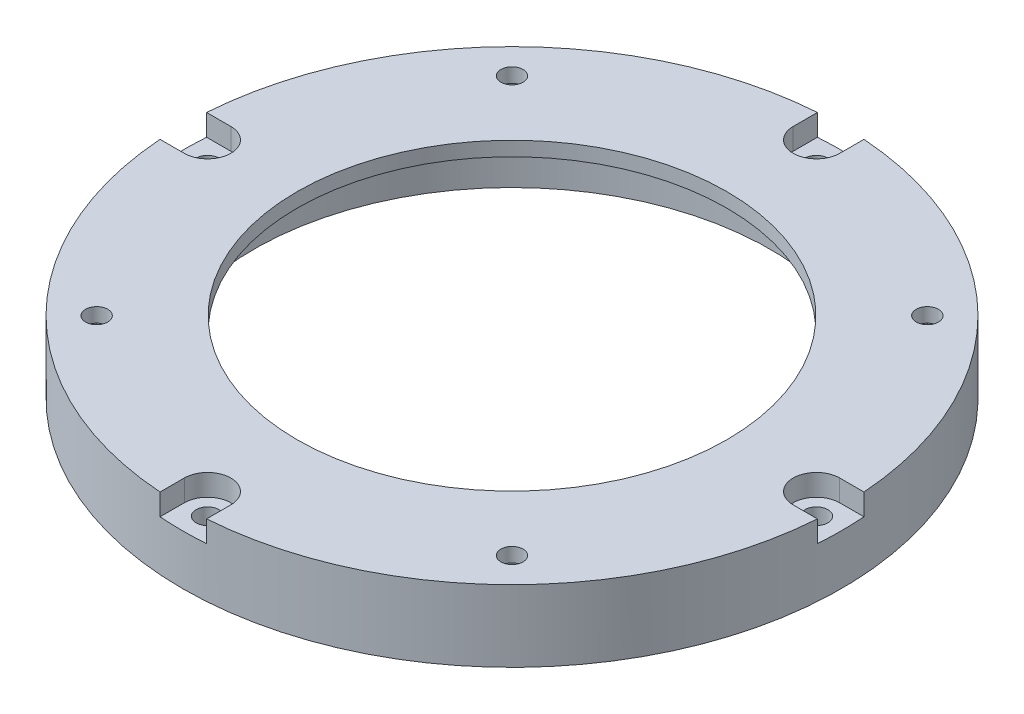
SolidWorks part; units mm, degrees
note: The reader was unsure of these and kept them because the rebuilt part matched: shared geometry of "Sketch1<3>", "Sketch9<3>".
ref_plane "Front Plane" through (0, 0, 0) normal (0, 0, 1) x (1, 0, 0)
ref_plane "Top Plane" through (0, 0, 0) normal (0, 1, 0) x (1, 0, 0)
ref_plane "Right Plane" through (0, 0, 0) normal (1, 0, 0) x (0, 0, -1)
sketch "Sketch1" plane through (0, 0, 0) normal (0, 1, 0) x (1, 0, 0)
  circle A0 centre (0, 0) radius 46
  circle A1 centre (0, 0) radius 36.05
  circle A2 centre (0, 0) radius 30
  dimension "D1" = 60
  dimension "D2" = 72.1
  dimension "D3" = 92
extrude "Boss-Extrude1" add sketch "Sketch1" against normal blind 2 contours A1 A2 | A0 A1
extrude "Boss-Extrude2" add sketch "Sketch1<3>" against normal blind 8 from surface at -2 contours A0 A1 starting at face at (0, -2, 30)
sketch "Sketch1<3>" plane through (0, 0, 0) normal (0, 1, 0) x (1, 0, 0) same geometry as "Sketch1"
hole_wizard "CBORE for M3 SHCS2" positions "Sketch6" profile "Sketch7" counterbore size "M3" standard "ANSI Metric" end condition through all
sketch "Sketch6" plane through (0, 0, 0) normal (0, 1, 0) x (1, 0, 0)
  line L0 (0, 0) -> (-42.5, 0) construction
  point P2 (-42.5, 0)
  dimension "D1" = 42.5
sketch "Sketch7" plane through (-42.5, 0, 0) normal (1, 0, 0) x (0, 0, 1)
  line L0 (0, 0) -> (0, 10)
  line L1 (0, 10) -> (1.6, 10)
  line L3 (1.6, 10) -> (1.6, 3)
  line L4 (1.6, 3) -> (3.25, 3)
  line L5 (3.25, 3) -> (3.25, 0)
  line L7 (3.25, 0) -> (0, 0)
  line L11 (0, -6.35) -> (0, 107.95) construction
  dimension "Thru Hole Dia." = 3.2
  dimension "Thru Hole Depth" = 10
  dimension "C'Bore Dia." = 6.5
  dimension "C'Bore Depth" = 3
sketch "Sketch8" plane through (0, -3, 0) normal (0, 1, 0) x (1, 0, 0)
  line L1 (-42.5, 3.25) -> (-52.5, 3.25)
  line L2 (-42.5, 3.25) -> (-42.5, -3.25)
  line L3 (-42.5, -3.25) -> (-52.5, -3.25)
  line L4 (-52.5, 3.25) -> (-52.5, -3.25)
  circle A3 centre (-42.5, 0) radius 3.25
  circle A5 centre (-42.5, 0) radius 3.25
  dimension "D2" = 10
  dimension "D1" = 0
extrude "Cut-Extrude1" cut sketch "Sketch8" along normal through all
pattern_circular "CirPattern1" count 4 over 360 about axis through (0, 0, 0) along (0, 1, 0) of "Cut-Extrude1", "CBORE for M3 SHCS2"
sketch "Sketch9" plane through (0, 0, 0) normal (0, 1, 0) x (1, 0, 0)
  line L0 (0, 0) -> (28.9914, 28.9914) construction
  line L1 (0, 0) -> (46, 0) construction
  line L2 (26.746, 31.2367) -> (25.9242, 28.1695)
  line L3 (25.9242, 28.1695) -> (28.1695, 25.9242)
  line L4 (28.1695, 25.9242) -> (31.2367, 26.746)
  line L5 (31.2367, 26.746) -> (32.0586, 29.8132)
  line L6 (32.0586, 29.8132) -> (29.8132, 32.0586)
  line L7 (29.8132, 32.0586) -> (26.746, 31.2367)
  circle A0 centre (28.9914, 28.9914) radius 1.55
  circle A1 centre (28.9914, 28.9914) radius 2.75 construction
  arc A2 (45.885, -3.25) -> (45.885, 3.25) centre (0, 0) ccw construction
  dimension "D2" = 3.1
  dimension "D1" = 41
  dimension "D3" = 5.5
  dimension "D4" = 45
extrude "Cut-Extrude2" cut sketch "Sketch9" against normal through all contours A0
extrude "Cut-Extrude3" cut sketch "Sketch9<3>" against normal through all from offset 2 contours L6 L7 L2 L3 L4 L5 A0 offset against normal yes
sketch "Sketch9<3>" plane through (0, 0, 0) normal (0, 1, 0) x (1, 0, 0) same geometry as "Sketch9"
pattern_circular "CirPattern2" count 4 over 360 about axis through (0, 0, 0) along (0, 1, 0) of "Cut-Extrude2", "Cut-Extrude3"
equation "\"Ratio\"= 15"
equation "\"Hull Diameter\"= 92"
equation "\"Fixed Ring Diameter\"= 76"
equation "\"Fixed Pin Diameter\"= 6"
equation "\"Output Ring Diameter\"= 40"
equation "\"Output Pin Diameter\"= 6"
equation "\"Disk Bearing Inner Diameter\"= 9"
equation "\"Disk Bearing Outer Diameter\"= 17"
equation "\"Disk Bearing Height\"= 5"
equation "\"Shaft Bearing Inner Diameter\"= 15"
equation "\"Shaft Bearing Outer Diameter\"= 21"
equation "\"Shaft Bearing Height\"= 4"
equation "\"Eccentricity\"= 1.5"
equation "\"Disk Height\"= 8"
equation "\"Disk Spacing\"= 5"
equation "\"Hull Height\"= 40"
equation "\"Shaft End Bearing Inner Diameter\"= 12"
equation "\"Shaft End Bearing Outer Diameter\"= 18"
equation "\"Shaft End Bearing Height\"= 4"
equation "\"Output Bearing Inner Diameter\"= 55"
equation "\"Output Bearing Outer Diameter\"= 72"
equation "\"Outer Bearing Height\"= 9"
equation "\"D1@Sketch1\"=\"Output Bearing Inner Diameter\"+5"
equation "\"D2@Sketch1\"=\"Output Bearing Outer Diameter\"+0.1"
equation "\"D3@Sketch1\"=\"Hull Diameter\""
